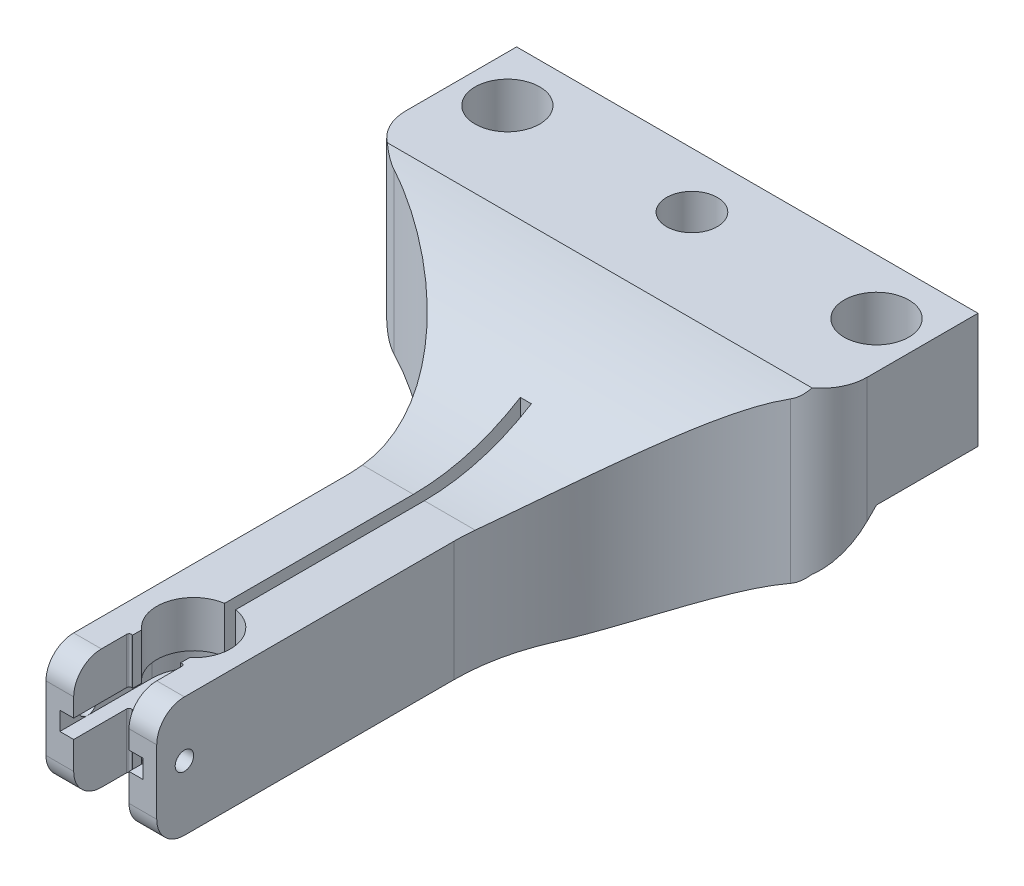
SolidWorks part; units mm, degrees
ref_plane "Front Plane" through (0, 0, 0) normal (0, 0, 1) x (1, 0, 0)
ref_plane "Top Plane" through (0, 0, 0) normal (0, 1, 0) x (1, 0, 0)
ref_plane "Right Plane" through (0, 0, 0) normal (1, 0, 0) x (0, 0, -1)
sketch "Sketch1" plane through (0, 0, 0) normal (0, 1, 0) x (1, 0, 0)
  line L0 (0, 0) -> (0, 54) construction
  line L1 (-20, 54) -> (20, 54) construction
  line L3 (-25, 60) -> (-25, 44)
  line L6 (-25, 60) -> (25, 60)
  line L7 (25, 60) -> (25, 44)
  line L11 (6, 44) -> (25, 44)
  line L12 (-6, 44) -> (-25, 44)
  line L13 (6, 44) -> (6, -10)
  line L14 (6, -10) -> (-6, -10)
  line L15 (-6, -10) -> (-6, 44)
  line L18 (0, 0) -> (0, -10) construction
  circle A1 centre (-20, 54) radius 3.5
  circle A2 centre (20, 54) radius 3.5
  circle A3 centre (0, 54) radius 2.75
  point P12 (0, 60)
  point P22 (0, -10)
  dimension "D3" = 10
  dimension "D4" = 16
  dimension "D5" = 7
  dimension "D6" = 7
  dimension "D7" = 5.5
  dimension "D2" = 12
  dimension "D9" = 10
  dimension "D10" = 40
  dimension "D11" = 50
  dimension "D16" = 54
extrude "Boss-Extrude1" add sketch "Sketch1" along normal blind 25 contours L11 L7 L6 L3 L12 A3 A2 A1 region at (0, 0, -35.0165)
fillet "Fillet8" radius 22 2 edges at (6, 12.5, -44) (-6, 12.5, -44)
sketch "Sketch2" plane through (0, 0, 0) normal (0, 1, 0) x (1, 0, 0)
  circle A0 centre (0, 0) radius 4
  dimension "D1" = 8
extrude "Cut-Extrude1" cut sketch "Sketch2" along normal up to surface (25 mm away) up to face at (0, 25, -51.25)
sketch "Sketch4" plane through (0, 0, 0) normal (0, -1, 0) x (-1, 0, 0)
  circle A0 centre (0, 0) radius 4.5
  dimension "D1" = 9
extrude "Cut-Extrude2" cut sketch "Sketch4" against normal blind 2 from offset 6 offset against normal yes
sketch "Sketch5" plane through (0, 25, 0) normal (0, 1, 0) x (1, 0, 0)
  line L0 (0, 36) -> (0, -10) construction
  line L1 (0, 36) -> (-0.6, 36)
  line L2 (-0.6, 36) -> (-0.6, 0)
  line L3 (-0.6, 0) -> (-2.6, 0)
  line L5 (-3, -10) -> (3, -10)
  line L7 (2.6, 0) -> (0.6, 0)
  line L8 (0.6, 0) -> (0.6, 36)
  line L9 (0.6, 36) -> (0, 36)
  line L10 (6, -10) -> (-6, -10) construction
  line L11 (-2.6, 0) -> (-2.6, -4)
  line L12 (-2.6, -4) -> (-3, -4)
  line L13 (-3, -4) -> (-3, -10)
  line L14 (2.6, 0) -> (2.6, -4)
  line L15 (2.6, -4) -> (3, -4)
  line L16 (3, -4) -> (3, -10)
  line L17 (6, -10) -> (-6, -10) construction
  point P2 (0, -10)
  dimension "D1" = 4
  dimension "D2" = 0.6
  dimension "D3" = 3
  dimension "D4" = 2
  dimension "D5" = 36
  dimension "D6" = 2
extrude "Cut-Extrude3" cut sketch "Sketch5" against normal up to surface (25 mm away) up to face at (0, 0, 4)
fillet "Fillet13" radius 0.25 2 edges at (3, 12.5, 4) (-3, 12.5, 4)
sketch "Sketch6" plane through (0, 0, 0) normal (0, 0, 1) x (1, 0, 0)
  line L1 (-4.5, 6) -> (4.5, 6)
  line L2 (-4.5, 6) -> (-4.5, 8)
  line L3 (-4.5, 8) -> (4.5, 8)
  line L4 (4.5, 6) -> (4.5, 8)
extrude "Cut-Extrude4" cut sketch "Sketch6" along normal blind 10
sketch "Sketch8" plane through (-6, 0, 0) normal (-1, 0, 0) x (0, 0, 1)
  line L1 (10, 0) -> (-22.2055, 0) construction
  line L2 (10, 25) -> (10, 0) construction
  circle A0 centre (7, 7) radius 1
  dimension "D1" = 2
  dimension "D2" = 3
  dimension "D3" = 7
extrude "Cut-Extrude5" cut sketch "Sketch8" against normal through all both and the other way through all
sketch "Sketch9" plane through (-25, 0, 0) normal (-1, 0, 0) x (0, 0, 1)
  line L0 (-44, 13) -> (10, 13)
  line L3 (10, 13) -> (10, 25)
  line L4 (10, 25) -> (-44, 25)
  line L5 (-44, 25) -> (-44, 13)
  dimension "D1" = 12
extrude "Cut-Extrude6" cut sketch "Sketch9" against normal up to surface (50 mm away) up to face at (25, 12.5, -52)
fillet "Fillet9" radius 22 1 edges at (0, 13, -44)
sketch "Sketch10" plane through (-25, 0, 0) normal (-1, 0, 0) x (0, 0, 1)
  line L0 (-44, 25) -> (-44, 0) construction
  line L1 (-60, 0) -> (-44, 0)
  line L2 (-60, 0) -> (-60, 12.5)
  line L3 (-60, 12.5) -> (-44, 12.5)
  line L4 (-44, 0) -> (-44, 12.5)
extrude "Cut-Extrude7" cut sketch "Sketch10" against normal up to surface (50 mm away) up to face at (25, 12.5, -52)
fillet "Fillet10" radius 5 1 edges at (0, 12.5, -44) profile chamfer
fillet "Fillet11" radius 15 1 edges at (0, 0, -44)
fillet "Fillet12" radius 5 2 edges at (25, 16.25, -44) (-25, 16.25, -44)
fillet "Fillet7" radius 3 4 edges at (-4.5, 0, 10) (4.5, 0, 10) (-4.5, 13, 10) (4.5, 13, 10)
sketch "Sketch12" plane through (0, -18.25, -18.25) normal (0, -0.7071, -0.7071) x (1, 0, 0)
  line L0 (0, -43.4871) -> (0, -36.416) construction
  line L1 (25, -43.4871) -> (-25, -43.4871) construction
  line L3 (-12.3319, -33.2654) -> (12.3319, -33.2654) construction
  text T0 "Jadhav Lab"
extrude "Boss-Extrude3" add sketch "Sketch12" along normal blind 0.8
